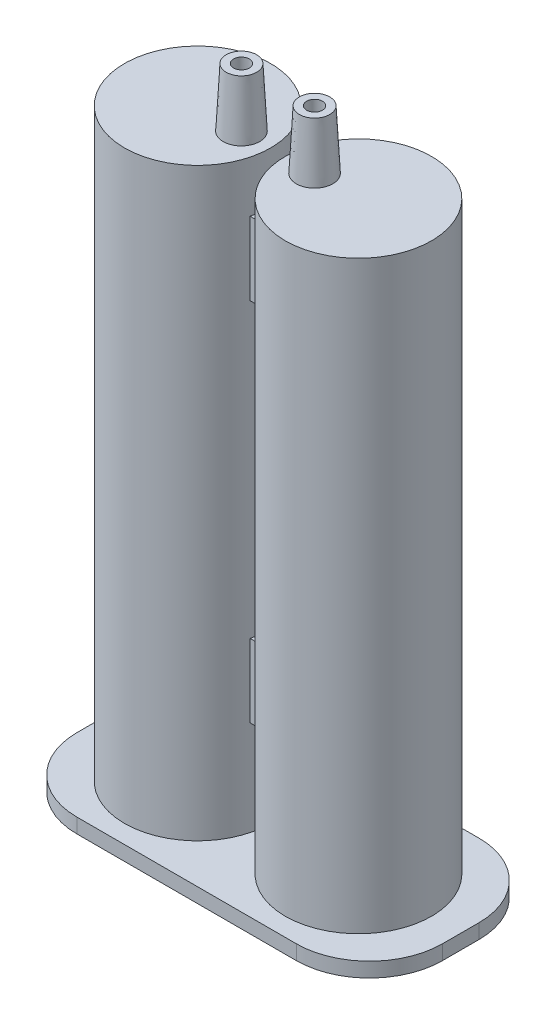
SolidWorks part; units mm, degrees
ref_plane "Front Plane" through (0, 0, 0) normal (0, 0, 1) x (1, 0, 0)
ref_plane "Top Plane" through (0, 0, 0) normal (0, 1, 0) x (1, 0, 0)
ref_plane "Right Plane" through (0, 0, 0) normal (1, 0, 0) x (0, 0, -1)
sketch "Sketch1" plane through (0, 0, 0) normal (0, 1, 0) x (1, 0, 0)
  line L1 (-15, -12.5) -> (15, -12.5)
  line L2 (-25, -2.5) -> (-25, 2.5)
  line L3 (-15, 12.5) -> (15, 12.5)
  line L4 (25, -2.5) -> (25, 2.5)
  line L5 (-25, -12.5) -> (25, 12.5) construction
  line L6 (-25, 12.5) -> (25, -12.5) construction
  arc A0 (15, 12.5) -> (25, 2.5) centre (15, 2.5) cw
  arc A1 (15, -12.5) -> (25, -2.5) centre (15, -2.5) ccw
  arc A2 (-15, -12.5) -> (-25, -2.5) centre (-15, -2.5) cw
  arc A3 (-25, 2.5) -> (-15, 12.5) centre (-15, 2.5) cw
  point P0 (0, 0)
  dimension "D3" = 10
  dimension "D1" = 50
  dimension "D2" = 25
extrude "Boss-Extrude1" add sketch "Sketch1" along normal blind 2
sketch "Sketch2" plane through (0, 2, 0) normal (0, 1, 0) x (1, 0, 0)
  line L0 (-25, 0) -> (25, 0) construction
  line L1 (-25, 2.5) -> (-25, -2.5) construction
  line L2 (25, -2.5) -> (25, 2.5) construction
  circle A0 centre (-11, 0) radius 10
  circle A1 centre (11, 0) radius 10
  circle A2 centre (-11, 0) radius 9
  circle A3 centre (11, 0) radius 9
  dimension "D3" = 20
  dimension "D4" = 20
  dimension "D5" = 1
  dimension "D6" = 1
  dimension "D1" = 11
  dimension "D2" = 11
extrude "Boss-Extrude2" add sketch "Sketch2" along normal blind 80 contours L0 A0 A2 | A0 L0 A2 | L0 A1 A3 | L0 A3 | A1 L0 A3 | L0 A2 | A2 L0 | A3 L0 region at (-11, 2, -9.2236) region at (-11, 2, 3.8197) region at (-11, 2, -3.8197) region at (-1.5, 2, 0.2236) region at (11, 2, -9.7764) region at (1.5, 2, 0.2236) region at (11, 2, -3.8197) region at (11, 2, 3.8197)
sketch "Sketch3" plane through (0, 82, 0) normal (0, 1, 0) x (1, 0, 0)
  line L0 (-11, 0) -> (11, 0) construction
  circle A0 centre (-5, 0) radius 2.5
  circle A1 centre (5, 0) radius 2.5
  dimension "D3" = 5
  dimension "D4" = 5
  dimension "D1" = 5
  dimension "D2" = 5
extrude "Boss-Extrude3" add sketch "Sketch3" along normal blind 8 draft 3
shell "Shell2" thickness 1 removed face at (-5, 90, 2.0807) removed face at (5, 90, 2.0807)
extrude "Cut-Extrude1" cut sketch "Sketch2<3>" against normal through all contours L0 A2 | A2 L0 | L0 A3 | A3 L0 region at (-11, 2, 3.8197) region at (-11, 2, -3.8197) region at (11, 2, -3.8197) region at (11, 2, 3.8197)
sketch "Sketch2<3>" plane through (0, 2, 0) normal (0, 1, 0) x (1, 0, 0) same geometry as "Sketch2"
ref_plane "Plane1" through (0, 20, 0) normal (0, 1, 0) x (1, 0, 0)
sketch "Sketch4" plane through (0, 20, 0) normal (0, 1, 0) x (1, 0, 0)
  line L0 (-25, 0) -> (25, 0) construction
  line L1 (-25, 2.5) -> (-25, -2.5) construction
  line L2 (25, -2.5) -> (25, 2.5) construction
  line L3 (-1.3175, 2.5) -> (1.3175, 2.5)
  line L4 (-1.3175, -2.5) -> (1.3175, -2.5)
  circle A0 centre (-11, 0) radius 10 construction
  circle A1 centre (11, 0) radius 10 construction
  arc A2 (-1.3175, 2.5) -> (-1.3175, -2.5) centre (-11, 0) cw
  arc A3 (1.3175, 2.5) -> (1.3175, -2.5) centre (11, 0) ccw
  dimension "D1" = 2.5
  dimension "D2" = 5
extrude "Boss-Extrude4" add sketch "Sketch4" along normal mid plane 10 contours L0 A2 L4 A3 | A2 L0 A3 L3 region at (0, 20, -1.3097) region at (0, 20, 1.3097)
ref_plane "Plane2" through (0, 70, 0) normal (0, 1, 0) x (1, 0, 0)
sketch "Sketch7" plane through (0, 70, 0) normal (0, 1, 0) x (1, 0, 0)
  line L0 (-25, 0) -> (25, 0) construction
  line L1 (-25, 2.5) -> (-25, -2.5) construction
  line L2 (25, -2.5) -> (25, 2.5) construction
  line L3 (-1.3175, 2.5) -> (1.3175, 2.5)
  line L4 (-1.3175, -2.5) -> (1.3175, -2.5)
  circle A0 centre (-11, 0) radius 10 construction
  circle A1 centre (11, 0) radius 10 construction
  circle A2 centre (11, 0) radius 10 construction
  arc A3 (-1.3175, 2.5) -> (-1.3175, -2.5) centre (-11, 0) cw
  arc A4 (-1.3175, -2.5) -> (-1.3175, 2.5) centre (-11, 0) ccw construction
  arc A5 (1.3175, 2.5) -> (1.3175, -2.5) centre (11, 0) ccw
  arc A6 (1.3175, 2.5) -> (1.3175, -2.5) centre (11, 0) ccw construction
  dimension "D1" = 5
  dimension "D2" = 2.5
extrude "Boss-Extrude5" add sketch "Sketch7" along normal mid plane 10 contours A3 L0 A5 L3 | L0 A3 L4 A5 region at (0, 70, -1.3097) region at (0, 70, 1.3097)
